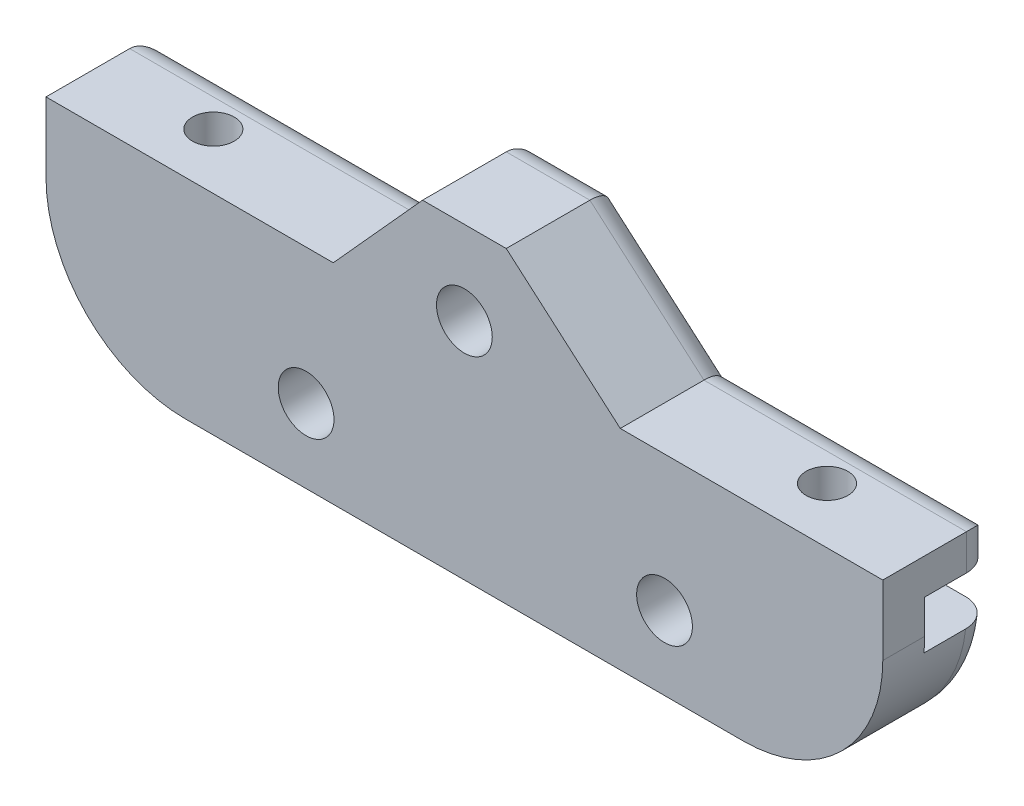
SolidWorks part; units mm, degrees
ref_plane "Plan de face" through (0, 0, 0) normal (0, 0, 1) x (1, 0, 0)
ref_plane "Plan de dessus" through (0, 0, 0) normal (0, 1, 0) x (1, 0, 0)
ref_plane "Plan de droite" through (0, 0, 0) normal (1, 0, 0) x (0, 0, -1)
sketch "Esquisse1" plane through (0, 0, 0) normal (0, 0, 1) x (1, 0, 0)
  line L0 (0, 10.8) -> (0, 0) construction
  line L10 (0, 0) -> (-11.35, 0) construction
  line L13 (0, 10.8) -> (0, 16.8) construction
  line L14 (0, 5.4) -> (-11.35, 0) construction
  line L15 (-11.35, 0) -> (-16.768, -2.5777) construction
  line L16 (-18.0569, 0.1313) -> (-15.4792, -5.2868)
  line L17 (3, 16.8) -> (-3, 16.8)
  line L18 (-18.0569, 0.1313) -> (-3, 16.8)
  line L22 (0, 0) -> (14.35, 0) construction
  line L24 (0, 5.4) -> (14.35, 0) construction
  line L25 (14.35, 0) -> (19.9656, -2.1132) construction
  line L26 (21.1598, 1.0604) -> (18.7713, -5.2868)
  line L27 (-15.4792, -5.2868) -> (18.7713, -5.2868)
  line L28 (3, 16.8) -> (21.1598, 1.0604)
  circle A1 centre (0, 10.8) radius 2 construction
  circle A2 centre (-11.35, 0) radius 2 construction
  circle A4 centre (14.35, 0) radius 2 construction
  point P7 (11.8631, -0.22)
  point P16 (-16.768, -2.5777)
  point P19 (0, 16.8)
  point P22 (19.9656, -2.1132)
  dimension "D2" = 4
  dimension "D10" = 4
  dimension "D6" = 6
  dimension "D4" = 6
  dimension "D3" = 6
  dimension "D5" = 6
  dimension "D7" = 25.7
  dimension "D8" = 14.35
  dimension "D9" = 10.8
  dimension "D11" = 6
extrude "Boss.-Extru.1" add sketch "Esquisse1" along normal blind 4 and the other way blind 4
sketch "Esquisse3" plane through (0, 0, 0) normal (0, 0, 1) x (1, 0, 0)
  line L0 (0, 10.8) -> (0, 0) construction
  line L2 (-11.35, 0) -> (0, 0) construction
  line L3 (0, 0) -> (14.35, 0) construction
  circle A0 centre (0, 10.8) radius 2
  circle A3 centre (-11.35, 0) radius 2
  circle A5 centre (14.35, 0) radius 2
  point P9 (0, -3)
  point P10 (0, 0)
  point P11 (0, 0)
  point P12 (0, 0)
  point P13 (0, -0.2567)
  dimension "D1" = 4
  dimension "D3" = 4
  dimension "D2" = 10.8
  dimension "D4" = 25.7
  dimension "D5" = 14.35
extrude "Enlèv. mat.-Extru.1" cut sketch "Esquisse3" against normal through all and the other way through all
sketch "Esquisse6" plane through (0, 0, 0) normal (0, 0, 1) x (1, 0, 0)
  line L3 (-9.4015, 9.7132) -> (-30, 9.7132)
  line L4 (-15.4792, -5.2868) -> (-30, -5.2868)
  line L5 (-30, -5.2868) -> (-30, 9.7132)
  line L6 (18.7713, -5.2868) -> (30, -5.2868)
  line L7 (30, -5.2868) -> (30, 9.7132)
  line L8 (30, 9.7132) -> (11.1765, 9.7132)
  line L9 (21.1598, 1.0604) -> (3, 16.8) construction
  line L10 (11.1765, 9.7132) -> (21.1598, 1.0604)
  line L11 (21.1598, 1.0604) -> (18.7713, -5.2868)
  line L12 (-9.4015, 9.7132) -> (-18.0569, 0.1313)
  line L13 (-3, 16.8) -> (-18.0569, 0.1313) construction
  line L14 (-18.0569, 0.1313) -> (-15.4792, -5.2868)
  dimension "D1" = 30
  dimension "D2" = 30
  dimension "D3" = 15
  dimension "D4" = 15
extrude "Boss.-Extru.2" add sketch "Esquisse6" along normal up to surface and the other way up to surface up to face at (2, 10.8, 4) other way up to face at (2, 10.8, -4)
sketch "Esquisse4" plane through (0, 0, 0) normal (0, 0, 1) x (1, 0, 0)
  line L0 (0, 0) -> (0, 5.4) construction
  line L2 (-30, 7.15) -> (30, 7.15)
  line L3 (-30, 7.15) -> (-30, 3.65)
  line L4 (-30, 3.65) -> (30, 3.65)
  line L5 (30, 7.15) -> (30, 3.65)
  line L6 (-30, 7.15) -> (30, 3.65) construction
  line L7 (-30, 3.65) -> (30, 7.15) construction
  circle A0 centre (14.35, 0) radius 2 construction
  point P7 (0, 7.2416)
  dimension "D3" = 5.4
  dimension "D1" = 3.5
  dimension "D2" = 60
extrude "Enlèv. mat.-Extru.2" cut sketch "Esquisse4" along normal blind 5 from surface starting at face at (0.2219, 7.7349, -4)
sketch "Esquisse7" plane through (0, 0, 0) normal (0, 1, 0) x (1, 0, 0)
  line L0 (0, 0) -> (0, 4) construction
  line L1 (3, 4) -> (-3, 4) construction
  line L2 (0, 0) -> (-22, 0) construction
  circle A0 centre (-22, 0) radius 1.5
  circle A1 centre (22, 0) radius 1.5
  dimension "D2" = 3
  dimension "D1" = 22
extrude "Enlèv. mat.-Extru.4" cut sketch "Esquisse7" against normal up to surface (-3.65 mm away) from surface up to face at (0, 3.65, -1.5) starting at face at (-19.7008, 9.7132, 0)
fillet "Congé1" radius 10 2 edges at (30, -5.2868, 0) (-30, -5.2868, 0)
fillet "Congé2" radius 2 10 edges at (-26.6846, -2.7243, -4) (26.6846, -2.7243, -4) (-6.2008, 13.2566, -4) (-19.7008, 9.7132, -4) (0, 16.8, -4) (7.0882, 13.2566, -4) (20.5882, 9.7132, -4) (0, -5.2868, -4) (-30, 8.4316, -4) (30, 8.4316, -4)
